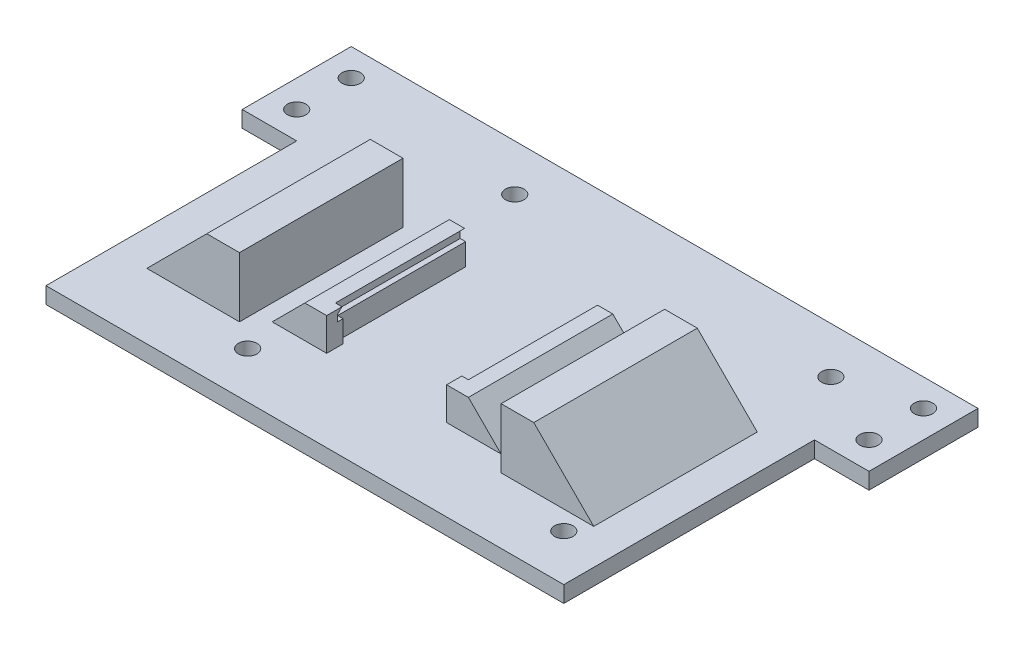
SolidWorks part; units mm, degrees
ref_plane "Front Plane" through (0, 0, 0) normal (0, 0, 1) x (1, 0, 0)
ref_plane "Top Plane" through (0, 0, 0) normal (0, 1, 0) x (1, 0, 0)
ref_plane "Right Plane" through (0, 0, 0) normal (1, 0, 0) x (0, 0, -1)
sketch "Sketch1" plane through (0, 0, 0) normal (0, 1, 0) x (1, 0, 0)
  line L0 (-57.5, 33) -> (-57.5, 13)
  line L1 (-57.5, -33) -> (57.5, -33) construction
  line L2 (-57.5, -33) -> (-57.5, 33) construction
  line L3 (-57.5, 33) -> (57.5, 33)
  line L4 (57.5, -33) -> (57.5, 33) construction
  line L5 (-57.5, -33) -> (57.5, 33) construction
  line L6 (-57.5, 33) -> (57.5, -33) construction
  line L7 (-57.5, 13) -> (-47.5, 13)
  line L8 (-47.5, 13) -> (-47.5, -33)
  line L9 (-47.5, -33) -> (47.5, -33)
  line L10 (47.5, -33) -> (47.5, 13)
  line L11 (47.5, 13) -> (57.5, 13)
  line L12 (57.5, 13) -> (57.5, 33)
  line L13 (-47.5, 13) -> (47.5, 13) construction
  point P0 (0, 0)
  dimension "D1" = 115
  dimension "D2" = 66
  dimension "D3" = 10
  dimension "D4" = 20
extrude "Boss-Extrude1" add sketch "Sketch1" along normal blind 3
hole_wizard "M3 Clearance Hole1" positions "Sketch2" profile "Sketch3" hole size "M3" standard "ISO" end condition through all
sketch "Sketch2" plane through (0, 3, 0) normal (0, 1, 0) x (1, 0, 0)
  line L0 (-57.5, 33) -> (-57.5, 13) construction
  line L1 (57.5, 33) -> (-57.5, 33) construction
  line L2 (-57.5, 13) -> (-47.5, 13) construction
  line L3 (57.5, 13) -> (57.5, 33) construction
  line L4 (47.5, 13) -> (57.5, 13) construction
  point P0 (-52.5, 28)
  point P2 (-52.5, 18)
  point P4 (52.5, 28)
  point P6 (52.5, 18)
  dimension "D1" = 5
  dimension "D2" = 5
  dimension "D3" = 5
  dimension "D4" = 5
  dimension "D5" = 5
  dimension "D6" = 5
  dimension "D7" = 5
  dimension "D8" = 5
sketch "Sketch3" plane through (-52.5, 3, -28) normal (1, 0, 0) x (0, 0, 1)
  line L0 (0, 0) -> (0, 3)
  line L1 (0, 3) -> (1.7, 3)
  line L2 (1.7, 3) -> (1.7, 0)
  line L5 (1.7, 0) -> (0, 0)
  line L11 (0, -6.35) -> (0, 107.95) construction
  dimension "Thru Hole Dia." = 3.4
  dimension "Thru Hole Depth" = 3
sketch "Sketch4" plane through (0, 3, 0) normal (0, 1, 0) x (1, 0, 0)
  line L1 (-42.5, -28) -> (42.5, -28)
  line L2 (-42.5, -28) -> (-42.5, 28)
  line L3 (-42.5, 28) -> (42.5, 28)
  line L4 (42.5, -28) -> (42.5, 28)
  line L5 (-42.5, -28) -> (42.5, 28) construction
  line L6 (-42.5, 28) -> (42.5, -28) construction
  point P0 (0, 0)
  dimension "D1" = 85
  dimension "D2" = 56
hole_wizard "M3 Clearance Hole2" positions "Sketch5" profile "Sketch6" hole size "M3" standard "ISO" end condition through all
sketch "Sketch5" plane through (0, 3, 0) normal (0, 1, 0) x (1, 0, 0)
  line L1 (-42.5, 28) -> (42.5, 28) construction
  line L2 (-42.5, -28) -> (42.5, -28) construction
  line L3 (42.5, -28) -> (42.5, 28) construction
  point P0 (-19, 24.5)
  point P2 (-19, -24.5)
  point P4 (39, -24.5)
  point P6 (39, 24.5)
  dimension "D1" = 3.5
  dimension "D2" = 61.5
  dimension "D3" = 3.5
  dimension "D4" = 61.5
  dimension "D5" = 3.5
  dimension "D6" = 3.5
  dimension "D7" = 3.5
  dimension "D8" = 3.5
sketch "Sketch6" plane through (-19, 3, -24.5) normal (1, 0, 0) x (0, 0, 1)
  line L0 (0, 0) -> (0, 3)
  line L1 (0, 3) -> (1.7, 3)
  line L2 (1.7, 3) -> (1.7, 0)
  line L5 (1.7, 0) -> (0, 0)
  line L11 (0, -6.35) -> (0, 107.95) construction
  dimension "Thru Hole Dia." = 3.4
  dimension "Thru Hole Depth" = 3
sketch "Sketch7" plane through (0, 3, 0) normal (0, 1, 0) x (1, 0, 0)
  line L0 (57.5, 33) -> (-57.5, 33) construction
  circle A0 centre (0, -6) radius 5
  point P4 (0, 33)
  dimension "D2" = 10
  dimension "D1" = 39
sketch "Sketch8" plane through (0, 3, 0) normal (0, 1, 0) x (1, 0, 0)
  line L0 (-12, -15) -> (12, -15)
  line L1 (-12, -15) -> (-12, 8.5)
  line L2 (-12, 8.5) -> (12, 8.5) construction
  line L3 (12, 8.5) -> (12, -15)
  point P2 (0, -15)
  dimension "D1" = 9
  dimension "D2" = 24
  dimension "D3" = 23.5
extrude "Extrude-Thin1" add sketch "Sketch8" along normal blind 6 thin thin type one direction reverse wall 3
sketch "Sketch9" plane through (0, 0, -8.5) normal (0, 0, -1) x (-1, 0, 0)
  line L0 (-12, 3) -> (-12, 7) construction
  line L1 (-12, 9) -> (-12, 3) construction
  line L3 (-12, 7) -> (-13, 7)
  line L4 (-12, 7) -> (-12, 8.2)
  line L5 (-12, 8.2) -> (-13, 8.2)
  line L6 (-13, 7) -> (-13, 8.2)
  dimension "D1" = 4
  dimension "D2" = 1
  dimension "D3" = 1.2
ref_plane "Plane1" through (0, 7.6, 0) normal (0, 1, 0) x (1, 0, 0)
sketch "Sketch10" plane through (0, 7.6, 0) normal (0, 1, 0) x (1, 0, 0)
  line L0 (12, 8.5) -> (12, -15)
  line L1 (12, -15) -> (-12, -15)
  line L2 (-12, -15) -> (-12, 8.5)
sweep "Cut-Sweep1" cut profiles "Sketch9" path "Sketch10"
chamfer "Chamfer1" distance 1 angle 45 3 edges at (-12, 8.2, 3.25) (0, 8.2, 15) (12, 8.2, 3.25)
sketch "Sketch11" plane through (0, 9, 0) normal (0, 1, 0) x (1, 0, 0)
  line L0 (15, -18) -> (-15, -18) construction
  line L1 (-11, -18) -> (11, -18)
  line L2 (-11, -18) -> (-11, -15)
  line L3 (-11, -15) -> (11, -15)
  line L4 (11, -18) -> (11, -15)
  point P6 (0, -18)
  dimension "D1" = 22
  dimension "D2" = 3
extrude "Cut-Extrude1" cut sketch "Sketch11" against normal blind 6
sketch "Sketch12" plane through (0, 3, 0) normal (0, 1, 0) x (1, 0, 0)
  line L0 (-47.5, -21) -> (-30, -21) construction
  line L1 (-30, 9) -> (-24, 9)
  line L2 (-30, 9) -> (-30, -21)
  line L3 (-30, -21) -> (-24, -21)
  line L4 (-24, 9) -> (-24, -21)
  line L5 (24, 9) -> (30, 9)
  line L6 (24, 9) -> (24, -21)
  line L7 (24, -21) -> (30, -21)
  line L8 (30, 9) -> (30, -21)
  line L10 (-47.5, 13) -> (-47.5, -33) construction
  line L12 (-47.5, -33) -> (47.5, -33) construction
  line L13 (30, -21) -> (47.5, -21) construction
  line L14 (47.5, -33) -> (47.5, 13) construction
  dimension "D1" = 60
  dimension "D2" = 6
  dimension "D3" = 30
  dimension "D4" = 12
extrude "Boss-Extrude3" add sketch "Sketch12" along normal blind 11
chamfer "Chamfer2" distance 6 angle 45 2 edges at (15, 3, 4.75) (-15, 3, 4.75)
chamfer "Chamfer3" distance 11 angle 45 2 edges at (30, 3, 6) (-30, 3, 6)
